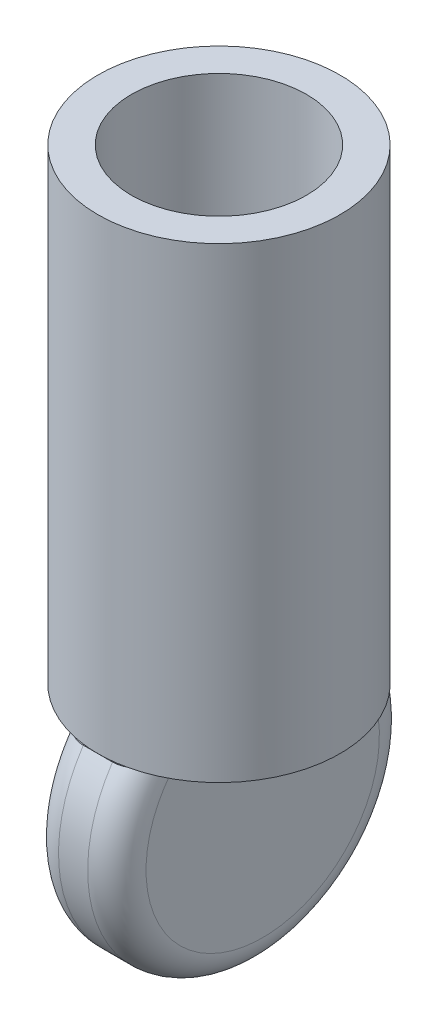
SolidWorks part; units mm, degrees
ref_plane "Front Plane" through (0, 0, 0) normal (0, 0, 1) x (1, 0, 0)
ref_plane "Top Plane" through (0, 0, 0) normal (0, 1, 0) x (1, 0, 0)
ref_plane "Right Plane" through (0, 0, 0) normal (1, 0, 0) x (0, 0, -1)
sketch "Sketch1" plane through (0, 0, 0) normal (0, 1, 0) x (1, 0, 0)
  circle A0 centre (0, 0) radius 4.15
  circle A1 centre (0, 0) radius 3
  dimension "D1" = 8.3
  dimension "D2" = 6
extrude "Boss-Extrude1" add sketch "Sketch1" along normal blind 14
extrude "Boss-Extrude2" add sketch "Sketch1<2>" against normal blind 2 contours A0 A1 | A1 region at (-4.0326, 0, 0) region at (0, 0, 0)
sketch "Sketch1<2>" plane through (0, 0, 0) normal (0, 1, 0) x (1, 0, 0) same geometry as "Sketch1"
sketch "Sketch3" plane through (0, 0, 0) normal (1, 0, 0) x (0, 0, -1)
  line L0 (-4.15, -2) -> (4.15, -2)
  line L1 (-4.15, -2) -> (4.15, -2) construction
  arc A0 (-4.15, -2) -> (4.15, -2) centre (0, -4.7888) ccw
  point P2 (4.15, -2)
  dimension "D1" = 10
extrude "Boss-Extrude3" add sketch "Sketch3" along normal mid plane 3
fillet "Fillet1" radius 1 2 edges at (-1.5, -9.7888, 0) (1.5, -9.7888, 0)
